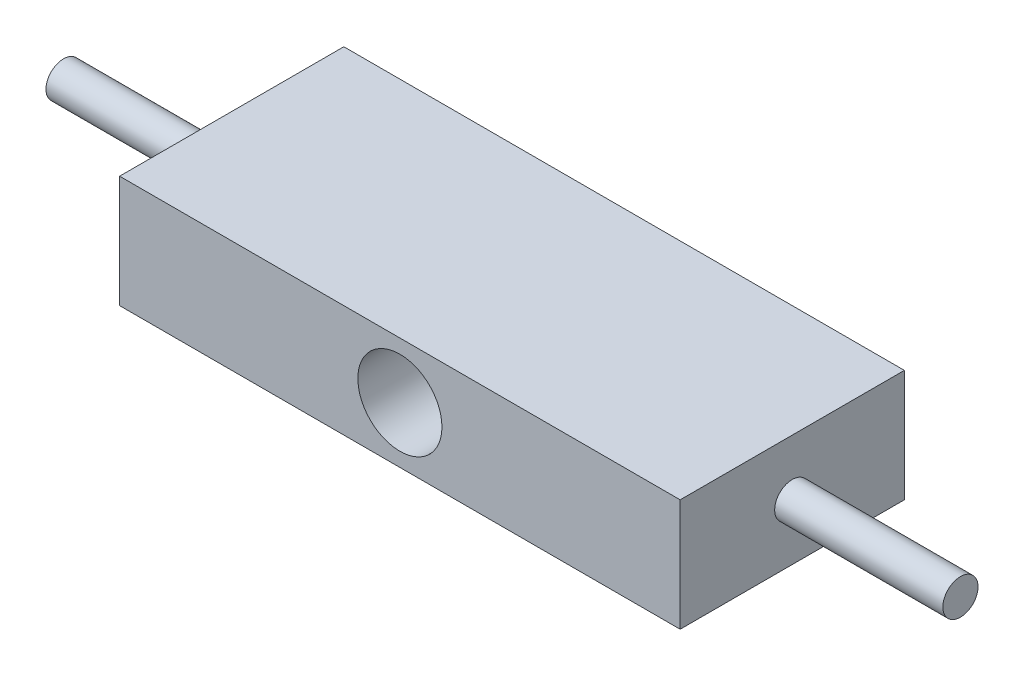
SolidWorks part; units mm, degrees
ref_plane "Front Plane" through (0, 0, 0) normal (0, 0, 1) x (1, 0, 0)
ref_plane "Top Plane" through (0, 0, 0) normal (0, 1, 0) x (1, 0, 0)
ref_plane "Right Plane" through (0, 0, 0) normal (1, 0, 0) x (0, 0, -1)
sketch "Sketch1" plane through (0, 0, 0) normal (0, 0, 1) x (1, 0, 0)
  line L1 (-31.75, 6.35) -> (31.75, 6.35)
  line L2 (-31.75, 6.35) -> (-31.75, -6.35)
  line L3 (-31.75, -6.35) -> (31.75, -6.35)
  line L4 (31.75, 6.35) -> (31.75, -6.35)
  line L5 (-31.75, 6.35) -> (31.75, -6.35) construction
  line L6 (-31.75, -6.35) -> (31.75, 6.35) construction
  circle A0 centre (0, 0) radius 4.7625
  point P0 (0, 0)
  dimension "D3" = 9.525
  dimension "D1" = 12.7
  dimension "D2" = 63.5
extrude "Boss-Extrude1" add sketch "Sketch1" against normal blind 25.4
sketch "Sketch2" plane through (31.75, 0, 0) normal (1, 0, 0) x (0, 0, -1)
  line L0 (0, 6.35) -> (25.4, -6.35) construction
  line L1 (25.4, 6.35) -> (0, -6.35) construction
  line L4 (0, 6.35) -> (0, -6.35)
  line L5 (0, -6.35) -> (25.4, -6.35)
  line L6 (25.4, -6.35) -> (25.4, 6.35)
  line L7 (25.4, 6.35) -> (0, 6.35)
  line L8 (0, 6.35) -> (0, -6.35)
  line L9 (0, -6.35) -> (25.4, -6.35)
  line L10 (25.4, -6.35) -> (25.4, 6.35)
  line L11 (25.4, 6.35) -> (0, 6.35)
  circle A0 centre (12.7, 0) radius 1.9939
  dimension "D2" = 3.9878
  dimension "D1" = 0
extrude "Boss-Extrude2" add sketch "Sketch2" along normal blind 19.05 contours A0 region at (31.75, 0, -12.7)
sketch "Sketch3" plane through (-31.75, 0, 0) normal (-1, 0, 0) x (0, 0, 1)
  line L0 (0, 6.35) -> (-25.4, -6.35) construction
  line L1 (-25.4, 6.35) -> (0, -6.35) construction
  line L2 (0, 6.35) -> (-25.4, -6.35)
  line L3 (-25.4, 6.35) -> (0, -6.35)
  line L4 (0, -6.35) -> (0, 6.35)
  line L5 (-25.4, -6.35) -> (0, -6.35)
  line L6 (-25.4, 6.35) -> (-25.4, -6.35)
  line L7 (0, 6.35) -> (-25.4, 6.35)
  line L8 (0, -6.35) -> (0, 6.35)
  line L9 (-25.4, -6.35) -> (0, -6.35)
  line L10 (-25.4, 6.35) -> (-25.4, -6.35)
  line L11 (0, 6.35) -> (-25.4, 6.35)
  circle A0 centre (-12.7, 0) radius 1.9939 construction
  circle A1 centre (-12.7, 0) radius 1.9939
  dimension "D1" = 0
extrude "Boss-Extrude3" add sketch "Sketch3" along normal blind 19.05 contours A1
